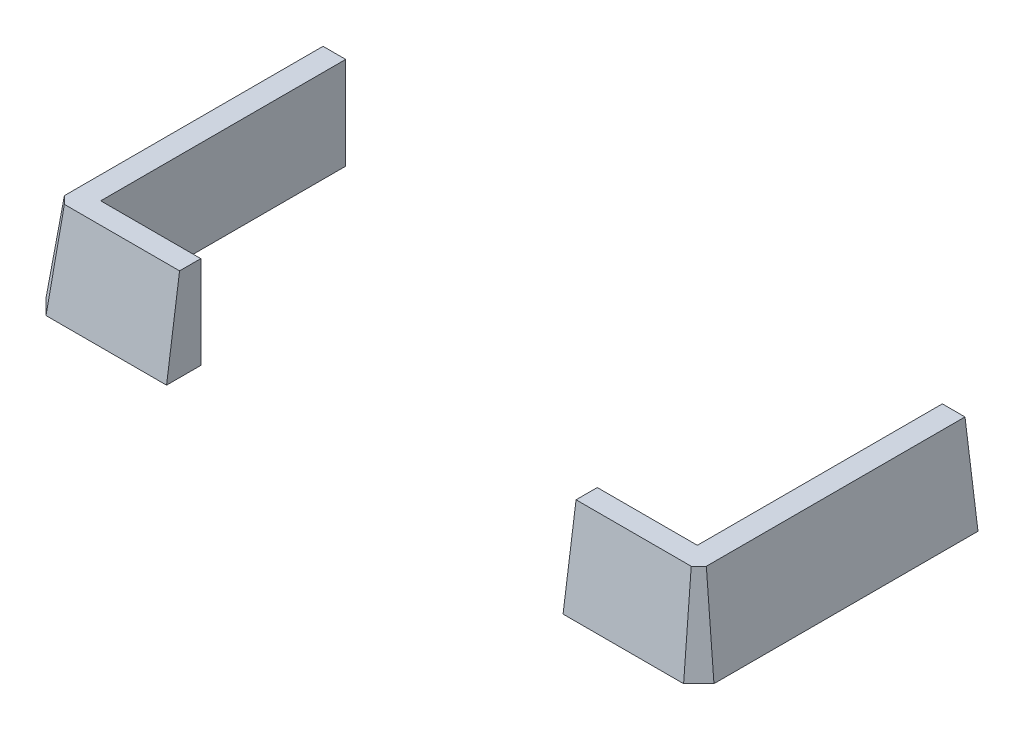
SolidWorks part; units mm, degrees
ref_plane "Front Plane" through (0, 0, 0) normal (0, 0, 1) x (1, 0, 0)
ref_plane "Top Plane" through (0, 0, 0) normal (0, 1, 0) x (1, 0, 0)
ref_plane "Right Plane" through (0, 0, 0) normal (1, 0, 0) x (0, 0, -1)
sketch "Sketch1" plane through (0, 0, 0) normal (0, 1, 0) x (1, 0, 0)
  line L9 (0, 0) -> (-158, 0) construction
  line L10 (0, 0) -> (0, 76.9384) construction
  line L11 (0, 0) -> (-158, 0) construction
  line L12 (-158, 99.7575) -> (-158, -30.0025) construction
  line L14 (-158, 99.7575) -> (-170, 99.7575) construction
  line L16 (-170, 99.7575) -> (-170, -41.2425) construction
  line L17 (-170, -41.2425) -> (-158, -41.2425) construction
  line L19 (-158, -30.0025) -> (-105, -30.0025) construction
  line L20 (-105, -30.0025) -> (-105, -41.2425) construction
  line L21 (-105, -41.2425) -> (-158, -41.2425) construction
  line L22 (-158, -30.0025) -> (-158, -41.2425) construction
  dimension "D5" = 158
  dimension "D6" = 12
  dimension "D7" = 53
  dimension "D8" = 11.24
  dimension "D9" = 41.2425
  dimension "D10" = 141
ref_plane "Plane1" through (0, -25, 0) normal (0, 1, 0) x (1, 0, 0)
ref_plane "Plane2" through (0, 24, 0) normal (0, 1, 0) x (1, 0, 0)
sketch "Sketch3" plane through (0, 24, 0) normal (0, 1, 0) x (1, 0, 0)
  line L0 (-170, 99.7575) -> (-158, 99.7575)
  line L1 (-158, 99.7575) -> (-158, -30.0025)
  line L2 (-158, -30.0025) -> (-105, -30.0025)
  line L3 (-105, -30.0025) -> (-105, -41.2425)
  line L4 (-105, -41.2425) -> (-166, -41.2425)
  line L5 (-170, -37.2425) -> (-170, 99.7575)
  line L6 (-166, -41.2425) -> (-170, -37.2425)
  point P11 (-170, -41.2425)
extrude "Boss-Extrude1" add sketch "Sketch3" against normal up to surface (49 mm away) up to plane "Plane1"
draft "Draft1" type of draft neutral plane draft angle 8 faces to draft 3 face at (-135.5, -0.5, 41.2425) face at (-168, -0.5, 39.2425) face at (-170, -0.5, -31.2575) neutral plane through (0, 24, 0) neutral plane normal (0, 1, 0) parameters "D1"=8
mirror "Mirror2" about plane through (0, 0, 0) normal (1, 0, 0) of bodies 105
